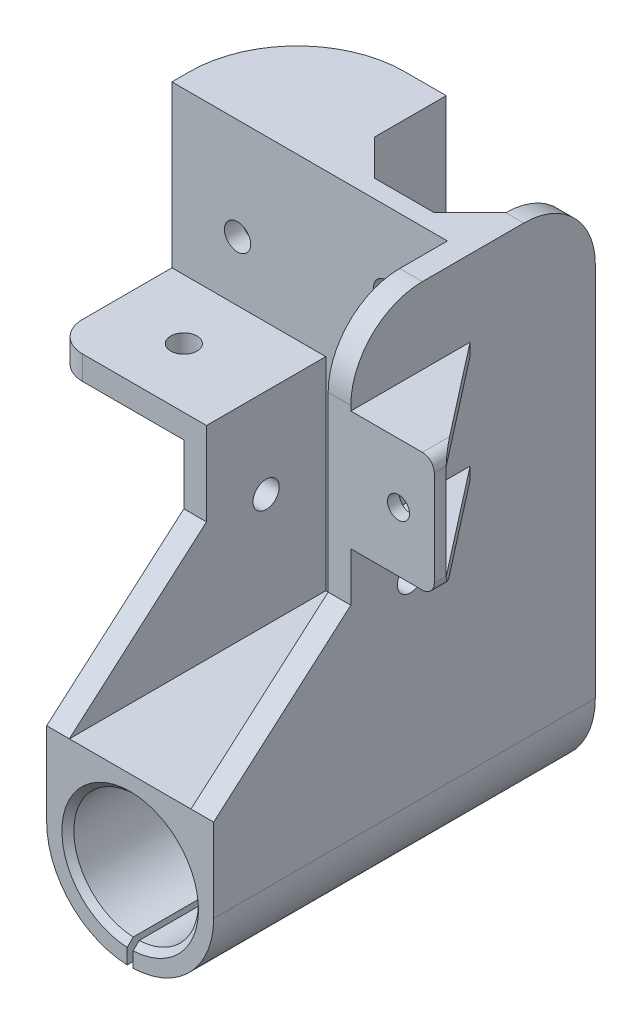
SolidWorks part; units mm, degrees
material "ABS"
ref_plane "Front Plane" through (0, 0, 0) normal (0, 0, 1) x (1, 0, 0)
ref_plane "Top Plane" through (0, 0, 0) normal (0, 1, 0) x (1, 0, 0)
ref_plane "Right Plane" through (0, 0, 0) normal (1, 0, 0) x (0, 0, -1)
sketch "Sketch1" plane through (0, 0, 0) normal (0, 0, 1) x (1, 0, 0)
  line L0 (-14, 0) -> (-14, 44)
  line L1 (-14, 44) -> (-36, 44)
  line L2 (-36, 44) -> (-36, 75)
  line L3 (-36, 75) -> (14, 75)
  line L4 (14, 75) -> (14, 0)
  arc A0 (-14, 0) -> (14, 0) centre (0, 0) ccw
  dimension "D3" = 28
  dimension "D1" = 31
  dimension "D2" = 22
  dimension "D4" = 75
extrude "Boss-Extrude1" add sketch "Sketch1" along normal blind 64
sketch "Sketch2" plane through (0, 75, 0) normal (0, 1, 0) x (1, 0, 0)
  line L0 (-11, 0) -> (-11, -12)
  line L1 (14, 0) -> (-36, 0) construction
  line L2 (-11, -12) -> (-5, -18)
  line L3 (-5, -18) -> (5, -18)
  line L4 (5, -18) -> (11, -12)
  line L5 (11, -12) -> (11, 0)
  line L6 (11, 0) -> (-11, 0)
  line L7 (14, -64) -> (14, 0) construction
  dimension "D1" = 10
  dimension "D2" = 22
  dimension "D3" = 3
  dimension "D4" = 12
  dimension "D5" = 18
extrude "Cut-Extrude1" cut sketch "Sketch2" against normal blind 61
sketch "Sketch3" plane through (14, 0, 0) normal (1, 0, 0) x (0, 0, -1)
  line L0 (-64, 14) -> (-41, 34)
  line L1 (-64, 0) -> (-64, 75) construction
  line L2 (-41, 34) -> (-41, 75)
  line L3 (-64, 75) -> (0, 75) construction
  line L4 (-41, 75) -> (-64, 75)
  line L5 (-64, 75) -> (-64, 14)
  dimension "D1" = 23
  dimension "D2" = 41
  dimension "D3" = 61
extrude "Cut-Extrude2" cut sketch "Sketch3" against normal through all
sketch "Sketch4" plane through (0, 0, 64) normal (0, 0, 1) x (1, 0, 0)
  line L0 (-10.2, 14) -> (-10.2, 48)
  line L1 (-14, 14) -> (14, 14) construction
  line L2 (-10.2, 48) -> (-36, 48)
  line L3 (-36, 44) -> (-36, 75) construction
  line L4 (-36, 48) -> (-36, 75)
  line L5 (-36, 75) -> (10.2, 75)
  line L6 (-36, 75) -> (14, 75) construction
  line L7 (10.2, 75) -> (10.2, 14)
  line L8 (10.2, 14) -> (-10.2, 14)
  line L9 (-14, 14) -> (-14, 34) construction
  line L10 (14, 14) -> (14, 34) construction
  line L11 (-14, 44) -> (-36, 44) construction
  dimension "D1" = 3.8
  dimension "D2" = 3.8
  dimension "D3" = 4
extrude "Cut-Extrude3" cut sketch "Sketch4" against normal blind 43
sketch "Sketch5" plane through (0, 0, 64) normal (0, 0, 1) x (1, 0, 0)
  line L0 (0, -10.45) -> (0, -14) construction
  line L1 (-0.5, -10.438) -> (-0.5, -13.9911)
  line L2 (0.5, -10.438) -> (0.5, -13.9911)
  line L3 (-0.5, -10.45) -> (-0.5, -17.5466) construction
  line L4 (0, -10.45) -> (0, -17.5466) construction
  line L5 (0.5, -10.45) -> (0.5, -17.5466) construction
  arc A0 (0.5, -10.438) -> (-0.5, -10.438) centre (0, 0) ccw
  arc A1 (-14, 0) -> (14, 0) centre (0, 0) ccw construction
  arc A2 (-0.5, -13.9911) -> (0.5, -13.9911) centre (0, 0) ccw
  dimension "D1" = 20.9
  dimension "D2" = 0.5
  dimension "D3" = 0.5
extrude "Cut-Extrude4" cut sketch "Sketch5" against normal through all
chamfer "Chamfer1" distance 1 angle 45 2 edges at (0, 10.45, 0) (0, 10.45, 64)
sketch "Sketch6" plane through (0, 0, 21) normal (0, 0, 1) x (1, 0, 0)
  line L0 (0, 14) -> (0, 27) construction
  line L1 (-10.2, 14) -> (10.2, 14) construction
  line L2 (-36, 48) -> (-10.2, 48) construction
  line L3 (-36, 75) -> (-36, 48) construction
  circle A0 centre (-25, 58) radius 2.2
  circle A1 centre (0, 62) radius 2.2
  circle A2 centre (0, 27) radius 2.2
  dimension "D1" = 4.4
  dimension "D2" = 35
  dimension "D4" = 10
  dimension "D5" = 11
  dimension "D3" = 13
extrude "Cut-Extrude5" cut sketch "Sketch6" against normal through all
sketch "Sketch7" plane through (14, 0, 0) normal (1, 0, 0) x (0, 0, -1)
  line L0 (-41, 62.2) -> (-21, 62.2)
  line L1 (-41, 34) -> (-41, 75) construction
  line L2 (-21, 62.2) -> (-21, 60.2)
  line L3 (-21, 60.2) -> (-39, 60.2)
  line L4 (-39, 60.2) -> (-39, 44.2)
  line L5 (-39, 44.2) -> (-21, 44.2)
  line L6 (-21, 44.2) -> (-21, 42.2)
  line L7 (-21, 42.2) -> (-41, 42.2)
  line L8 (-41, 42.2) -> (-41, 62.2)
  line L9 (-41, 75) -> (0, 75) construction
  dimension "D1" = 20
  dimension "D2" = 12.8
  dimension "D3" = 2
  dimension "D4" = 2
extrude "Boss-Extrude2" add sketch "Sketch7" along normal blind 14
sketch "Sketch8" plane through (0, 62.2, 0) normal (0, 1, 0) x (1, 0, 0)
  line L0 (14, -21) -> (28, -39)
  line L1 (28, -21) -> (28, -41) construction
  line L2 (28, -39) -> (28, -21)
  line L3 (28, -21) -> (14, -21)
  line L4 (28, -41) -> (14, -41) construction
  dimension "D1" = 2
extrude "Cut-Extrude6" cut sketch "Sketch8" against normal through all
sketch "Sketch9" plane through (0, 0, 41) normal (0, 0, 1) x (1, 0, 0)
  line L0 (22, 52.2) -> (28, 52.2) construction
  line L1 (28, 62.2) -> (28, 42.2) construction
  circle A0 centre (22, 52.2) radius 1.85
  dimension "D1" = 3.7
  dimension "D2" = 6
extrude "Cut-Extrude7" cut sketch "Sketch9" against normal through all
fillet "Fillet1" radius 2 2 edges at (28, 42.2, 40) (28, 62.2, 40)
fillet "Fillet2" radius 12 2 edges at (12.5, 75, 0) (12.1, 75, 41)
sketch "Sketch10" plane through (14, 0, 0) normal (1, 0, 0) x (0, 0, -1)
  line L0 (0, 0) -> (0, 63) construction
  line L1 (-29, 75) -> (-12, 75) construction
  circle A0 centre (-31, 33) radius 2.2
  dimension "D1" = 4.4
  dimension "D2" = 31
  dimension "D3" = 42
extrude "Cut-Extrude8" cut sketch "Sketch10" against normal through all
fillet "Fillet3" radius 5 1 edges at (-36, 46, 41)
fillet "Fillet4" radius 18 1 edges at (-36, 59.5, 0)
sketch "Sketch11" plane through (0, 48, 0) normal (0, 1, 0) x (1, 0, 0)
  line L0 (-36, -21) -> (-36, -36) construction
  line L1 (-10.2, -41) -> (-31, -41) construction
  circle A0 centre (-24, -31) radius 2.2
  dimension "D1" = 4.4
  dimension "D3" = 10
  dimension "D2" = 12
extrude "Cut-Extrude9" cut sketch "Sketch11" against normal through all
sketch "Sketch12" plane through (-36, 0, 0) normal (-1, 0, 0) x (0, 0, 1)
  line L0 (18, 75) -> (18, 44) construction
  line L1 (18, 71) -> (0, 71)
  line L2 (18, 71) -> (18, 48)
  line L3 (18, 48) -> (0, 48)
  line L4 (0, 71) -> (0, 48)
  line L5 (0, 44) -> (0, 75) construction
  line L6 (18, 75) -> (0, 75) construction
  line L7 (0, 44) -> (18, 44) construction
  dimension "D1" = 4
  dimension "D2" = 4
extrude "Cut-Extrude10" cut sketch "Sketch12" against normal blind 22
